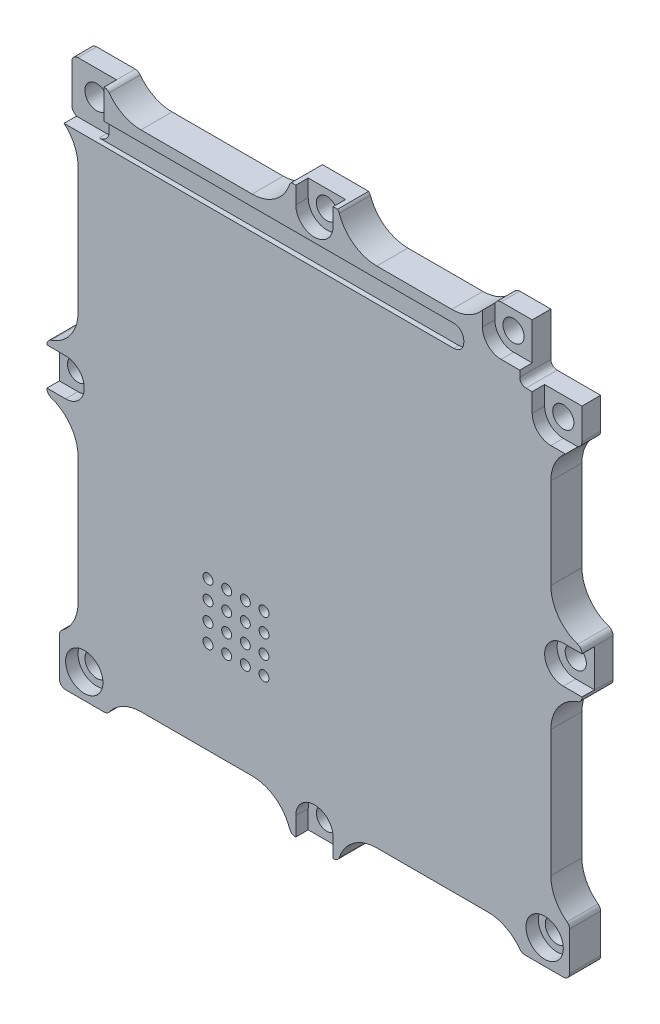
SolidWorks part; units mm, degrees
material "6061-T6 (SS)"
ref_plane "Front Plane" through (0, 0, 0) normal (0, 0, 1) x (1, 0, 0)
ref_plane "Top Plane" through (0, 0, 0) normal (0, 1, 0) x (1, 0, 0)
ref_plane "Right Plane" through (0, 0, 0) normal (1, 0, 0) x (0, 0, -1)
sketch "Sketch1" plane through (0, 0, 0) normal (0, 0, 1) x (1, 0, 0)
  line L0 (43, 3.0525) -> (43, -3.0525)
  line L1 (-40, 43.5) -> (-9.9117, 43.5) construction
  line L2 (-41, 42.5) -> (-41, 9.9642) construction
  line L3 (-40, -43.5) -> (-9.9117, -43.5) construction
  line L4 (41, 35.5) -> (41, 10.6494) construction
  line L5 (-43, -3.0525) -> (-43, 3.0525)
  line L6 (3.0525, -45.5) -> (-3.0525, -45.5)
  line L7 (3.0525, 45.5) -> (-3.0525, 45.5)
  line L8 (41, -24.3564) -> (41, -42.5) construction
  line L9 (10.0167, -43.5) -> (40, -43.5) construction
  line L10 (-41, -9.9642) -> (-41, -42.5) construction
  line L11 (10.0167, 43.5) -> (33, 43.5) construction
  line L12 (38, 24.5755) -> (38, 10.0167)
  line L14 (41, 35.5) -> (41, 30.5)
  line L15 (22.0755, 40.5) -> (10.0167, 40.5)
  line L17 (33, 43.5) -> (28, 43.5)
  line L18 (38, -10.0167) -> (38, -30.3815)
  line L20 (41, -42.5) -> (41, -36.3061)
  line L21 (-10.0167, 40.5) -> (-27.8815, 40.5)
  line L22 (-40, 43.5) -> (-33.8061, 43.5)
  line L23 (-41, 42.5) -> (-41, 36.3061)
  line L24 (-38, 30.3815) -> (-38, 10.0167)
  line L25 (-38, -10.0167) -> (-38, -30.3815)
  line L26 (-41, -42.5) -> (-41, -36.3061)
  line L27 (-40, -43.5) -> (-33.8061, -43.5)
  line L28 (-10.0167, -40.5) -> (-27.8815, -40.5)
  line L29 (27.8815, -40.5) -> (10.0167, -40.5)
  line L30 (40, -43.5) -> (33.8061, -43.5)
  line L31 (33, 43.5) -> (33, 36.5)
  line L32 (41, 35.5) -> (34, 35.5)
  arc A0 (-41, -42.5) -> (-40, -43.5) centre (-40, -42.5) ccw
  arc A1 (40, -43.5) -> (41, -42.5) centre (40, -42.5) ccw
  arc A3 (-40, 43.5) -> (-41, 42.5) centre (-40, 42.5) ccw
  circle A12 centre (40, 0) radius 1.7
  circle A13 centre (0, 42.5) radius 1.7
  circle A14 centre (-40, 0) radius 1.7
  circle A15 centre (0, -42.5) radius 1.7
  arc A24 (4, 44.8197) -> (3.0525, 45.5) centre (3.0525, 44.5) ccw
  arc A25 (-3.0525, 45.5) -> (-4, 44.8197) centre (-3.0525, 44.5) ccw
  arc A26 (43, -3.0525) -> (42.3197, -4) centre (42, -3.0525) cw
  arc A27 (43, 3.0525) -> (42.3197, 4) centre (42, 3.0525) ccw
  arc A28 (4, -44.8197) -> (3.0525, -45.5) centre (3.0525, -44.5) cw
  arc A29 (-3.0525, -45.5) -> (-4, -44.8197) centre (-3.0525, -44.5) cw
  arc A30 (-43, -3.0525) -> (-42.3197, -4) centre (-42, -3.0525) ccw
  arc A31 (-42.3197, 4) -> (-43, 3.0525) centre (-42, 3.0525) ccw
  arc A32 (41, 30.5) -> (40.5918, 29.6939) centre (40, 30.5) cw
  arc A33 (40.5918, 29.6939) -> (38, 24.5755) centre (44.35, 24.5755) ccw
  arc A34 (42.3197, 4) -> (38, 10.0167) centre (44.35, 10.0167) cw
  arc A35 (22.0755, 40.5) -> (27.1939, 43.0918) centre (22.0755, 46.85) ccw
  arc A36 (28, 43.5) -> (27.1939, 43.0918) centre (28, 42.5) ccw
  arc A37 (10.0167, 40.5) -> (4, 44.8197) centre (10.0167, 46.85) cw
  arc A38 (42.3197, -4) -> (38, -10.0167) centre (44.35, -10.0167) ccw
  arc A39 (38, -30.3815) -> (40.5918, -35.5) centre (44.35, -30.3815) ccw
  arc A40 (41, -36.3061) -> (40.5918, -35.5) centre (40, -36.3061) ccw
  arc A41 (-10.0167, 40.5) -> (-4, 44.8197) centre (-10.0167, 46.85) ccw
  arc A42 (-33.8061, 43.5) -> (-33, 43.0918) centre (-33.8061, 42.5) cw
  arc A43 (-41, 36.3061) -> (-40.5918, 35.5) centre (-40, 36.3061) ccw
  arc A44 (-27.8815, 40.5) -> (-33, 43.0918) centre (-27.8815, 46.85) cw
  arc A45 (-38, 30.3815) -> (-40.5918, 35.5) centre (-44.35, 30.3815) ccw
  arc A46 (-42.3197, 4) -> (-38, 10.0167) centre (-44.35, 10.0167) ccw
  arc A47 (-42.3197, -4) -> (-38, -10.0167) centre (-44.35, -10.0167) cw
  arc A48 (-41, -36.3061) -> (-40.5918, -35.5) centre (-40, -36.3061) cw
  arc A49 (-38, -30.3815) -> (-40.5918, -35.5) centre (-44.35, -30.3815) cw
  arc A50 (-33.8061, -43.5) -> (-33, -43.0918) centre (-33.8061, -42.5) ccw
  arc A51 (-27.8815, -40.5) -> (-33, -43.0918) centre (-27.8815, -46.85) ccw
  arc A52 (-4, -44.8197) -> (-10.0167, -40.5) centre (-10.0167, -46.85) ccw
  arc A53 (10.0167, -40.5) -> (4, -44.8197) centre (10.0167, -46.85) ccw
  arc A54 (33.8061, -43.5) -> (33, -43.0918) centre (33.8061, -42.5) cw
  arc A55 (27.8815, -40.5) -> (33, -43.0918) centre (27.8815, -46.85) cw
  arc A56 (33, 36.5) -> (34, 35.5) centre (34, 36.5) ccw
  circle A57 centre (30, 40.5) radius 1.7
  circle A58 centre (38, 32.5) radius 1.7
  point P9 (-41, -43.5)
  point P14 (41, 43.5)
  point P17 (-41, 43.5)
  point P26 (43, 0)
  point P27 (-43, 0)
  point P28 (0, -45.5)
  point P29 (0, 45.5)
  dimension "D3" = 1
  dimension "D4" = 3
  dimension "D11" = 3
  dimension "D12" = 3.4
  dimension "D19" = 38
  dimension "D20" = 1
  dimension "D23" = 6.35
  dimension "D24" = 1
  dimension "D28" = 6.35
  dimension "D31" = 1
  dimension "D5" = 3
  dimension "D6" = 3
  dimension "D7" = 3
  dimension "D8" = 76
  dimension "D9" = 81
  dimension "D10" = 3
  dimension "D13" = 2
  dimension "D14" = 2
  dimension "D15" = 2
  dimension "D16" = 2
  dimension "D17" = 3
  dimension "D18" = 3
  dimension "D21" = 8
  dimension "D22" = 40.5
  dimension "D25" = 5
  dimension "D26" = 5
  dimension "D27" = 5
  dimension "D29" = 5
  dimension "D30" = 5
  dimension "D32" = 5
  dimension "D33" = 5
  dimension "D34" = 5
  dimension "D35" = 5
  dimension "D36" = 3
  dimension "D37" = 3
  dimension "D38" = 3
  dimension "D39" = 3
extrude "Boss-Extrude1" add sketch "Sketch1" against normal blind 5
sketch "Sketch2" plane through (0, 0, -5) normal (0, 0, -1) x (-1, 0, 0)
  line L0 (-20, 37.5) -> (20, 37.5)
  line L1 (35, 22.5) -> (35, -22.5)
  line L2 (-20, -37.5) -> (20, -37.5)
  line L3 (-35, -22.5) -> (-35, 22.5)
  arc A1 (-20, 37.5) -> (-35, 22.5) centre (-20, 22.5) ccw
  arc A3 (20, 37.5) -> (35, 22.5) centre (20, 22.5) cw
  arc A7 (35, -22.5) -> (20, -37.5) centre (20, -22.5) cw
  arc A9 (-35, -22.5) -> (-20, -37.5) centre (-20, -22.5) ccw
  point P13 (35, 0)
  point P14 (0, 37.5)
  dimension "D1" = 15
  dimension "D2" = 70
  dimension "D3" = 75
extrude "Cut-Extrude1" cut sketch "Sketch2" against normal blind 2 contours L0 A3 L1 A7 L2 A9 L3 A1
sketch "Sketch3" plane through (0, 0, 0) normal (0, 0, 1) x (1, 0, 0)
  line L0 (33.8061, -43.5) -> (40, -43.5) construction
  line L1 (40, 3) -> (43, 3)
  line L2 (40, -3) -> (43, -3)
  line L3 (43, 3) -> (43, -3)
  line L4 (43, -3.0525) -> (43, 3.0525) construction
  line L5 (-40, 3) -> (-43, 3)
  line L6 (-40, -3) -> (-43, -3)
  line L7 (-43, -3) -> (-43, 3)
  line L8 (-43, 3.0525) -> (-43, -3.0525) construction
  line L9 (41, -42.5) -> (41, -36.3061) construction
  line L10 (-40, -43.5) -> (-33.8061, -43.5) construction
  line L11 (-41, -36.3061) -> (-41, -42.5) construction
  line L12 (-41, 42.5) -> (-41, 36.3061) construction
  line L13 (-33.8061, 43.5) -> (-40, 43.5) construction
  line L16 (-3, 42.5) -> (-3, 45.5)
  line L17 (3, 42.5) -> (3, 45.5)
  line L18 (-3, 45.5) -> (3, 45.5)
  line L19 (3.0525, 45.5) -> (-3.0525, 45.5) construction
  line L20 (-3, -42.5) -> (-3, -45.5)
  line L21 (3, -42.5) -> (3, -45.5)
  line L22 (-3, -45.5) -> (3, -45.5)
  line L23 (-3.0525, -45.5) -> (3.0525, -45.5) construction
  line L24 (38, 29.5) -> (40.3411, 29.5)
  line L25 (35, 32.5) -> (35, 35.5)
  line L26 (41, 35.5) -> (34, 35.5) construction
  line L27 (30, 37.5) -> (33, 37.5)
  line L28 (33, 36.5) -> (33, 43.5) construction
  line L29 (27, 40.5) -> (27, 42.8411)
  line L30 (41, 30.5) -> (41, 35.5) construction
  line L31 (33, 43.5) -> (28, 43.5) construction
  line L32 (41, 35.5) -> (35, 35.5)
  line L33 (41, 30.5) -> (41, 35.5)
  line L34 (33, 37.5) -> (33, 43.5)
  line L35 (33, 43.5) -> (28, 43.5)
  arc A0 (-40, -3) -> (-40, 3) centre (-40, 0) ccw
  arc A1 (-3, 42.5) -> (3, 42.5) centre (0, 42.5) ccw
  arc A2 (40, 3) -> (40, -3) centre (40, 0) ccw
  arc A3 (3, -42.5) -> (-3, -42.5) centre (0, -42.5) ccw
  circle A5 centre (-37, 39.5) radius 3
  circle A6 centre (-37, -39.5) radius 3
  circle A7 centre (37, -39.5) radius 3
  arc A8 (27, 40.5) -> (30, 37.5) centre (30, 40.5) ccw
  arc A9 (35, 32.5) -> (38, 29.5) centre (38, 32.5) ccw
  circle A10 centre (30, 40.5) radius 1.7 construction
  circle A11 centre (38, 32.5) radius 1.7 construction
  arc A16 (40.5918, 29.6939) -> (38, 24.5755) centre (44.35, 24.5755) ccw construction
  arc A17 (22.0755, 40.5) -> (27.1939, 43.0918) centre (22.0755, 46.85) ccw construction
  arc A18 (40.5918, 29.6939) -> (41, 30.5) centre (40, 30.5) ccw construction
  arc A19 (28, 43.5) -> (27.1939, 43.0918) centre (28, 42.5) ccw construction
  arc A20 (40.5918, 29.6939) -> (41, 30.5) centre (40, 30.5) ccw
  arc A21 (40.5918, 29.6939) -> (40.3411, 29.5) centre (44.35, 24.5755) ccw
  arc A22 (28, 43.5) -> (27.1939, 43.0918) centre (28, 42.5) ccw
  arc A23 (27, 42.8411) -> (27.1939, 43.0918) centre (22.0755, 46.85) ccw
  dimension "D1" = 6
  dimension "D2" = 4
  dimension "D3" = 4
  dimension "D6" = 4
  dimension "D7" = 4
  dimension "D8" = 4
  dimension "D9" = 4
extrude "Cut-Extrude2" cut sketch "Sketch3" against normal blind 2
sketch "Sketch4" plane through (0, 0, -2) normal (0, 0, 1) x (1, 0, 0)
  circle A0 centre (-37, 39.5) radius 1.9
  circle A2 centre (37, -39.5) radius 1.9
  circle A3 centre (-37, -39.5) radius 1.9
  circle A4 centre (-37, 39.5) radius 3 construction
  circle A6 centre (-37, -39.5) radius 3 construction
  circle A7 centre (37, -39.5) radius 3 construction
  dimension "D1" = 3.8
extrude "Cut-Extrude3" cut sketch "Sketch4" against normal up to surface (3 mm away) up to face at (0, 0, -5)
sketch "Sketch5" plane through (0, 0, 0) normal (0, 0, 1) x (1, 0, 0)
  line L0 (-17.109, -19.609) -> (-34, -19.609) construction
  line L1 (-17.109, -19.609) -> (-14.109, -19.609) construction
  line L2 (20, -37.5) -> (-20, -37.5) construction
  line L3 (-35, 22.5) -> (-35, -22.5) construction
  line L4 (-17.109, -19.609) -> (-17.109, -22.609) construction
  line L5 (-17.109, -19.609) -> (-17.109, -16.609) construction
  circle A0 centre (-17.109, -19.609) radius 16.891 construction
  circle A2 centre (-17.109, -19.609) radius 0.8
  circle A3 centre (-14.109, -19.609) radius 0.8
  circle A4 centre (-11.109, -19.609) radius 0.8
  circle A5 centre (-8.109, -19.609) radius 0.8
  circle A6 centre (-17.109, -22.609) radius 0.8
  circle A7 centre (-14.109, -22.609) radius 0.8
  circle A8 centre (-11.109, -22.609) radius 0.8
  circle A9 centre (-8.109, -22.609) radius 0.8
  circle A10 centre (-17.109, -25.609) radius 0.8
  circle A11 centre (-14.109, -25.609) radius 0.8
  circle A12 centre (-11.109, -25.609) radius 0.8
  circle A13 centre (-8.109, -25.609) radius 0.8
  circle A14 centre (-17.109, -16.609) radius 0.8
  circle A15 centre (-14.109, -16.609) radius 0.8
  circle A16 centre (-11.109, -16.609) radius 0.8
  circle A17 centre (-8.109, -16.609) radius 0.8
  dimension "D6" = 3
  dimension "D7" = 16.891
  dimension "D9" = 3
  dimension "D2" = 1.6
  dimension "D3" = 4
  dimension "D4" = 3
  dimension "D5" = 3
  dimension "D8" = 2
  dimension "D10" = 17.891
  dimension "D11" = 17.891
extrude "Cut-Extrude4" cut sketch "Sketch5" against normal up to surface (3 mm away) up to face at (0, 0, -3)
sketch "Sketch7" plane through (0, 0, 0) normal (0, 0, 1) x (1, 0, 0)
  line L0 (-10.0167, 40.5) -> (-27.8815, 40.5) construction
  line L1 (22.4125, 38.73) -> (-34.1005, 38.73)
  line L2 (24, 37.1425) -> (24, 36.8175)
  line L3 (22.4125, 35.23) -> (-37, 35.23)
  line L5 (38, 10.0167) -> (38, 24.5755) construction
  line L6 (-37, 36.5) -> (-37, 35.23)
  circle A2 centre (-37, 39.5) radius 3 construction
  arc A3 (-37, 36.5) -> (-34.1005, 38.73) centre (-37, 39.5) ccw
  arc A4 (22.4125, 38.73) -> (24, 37.1425) centre (22.4125, 37.1425) cw
  arc A5 (24, 36.8175) -> (22.4125, 35.23) centre (22.4125, 36.8175) cw
  dimension "D4" = 1.5875
  dimension "D1" = 3.5
  dimension "D2" = 1.77
  dimension "D3" = 14
extrude "Cut-Extrude8" cut sketch "Sketch7" against normal blind 0.8 contours L3 L6 A3 L1 A4 L2 A5
fillet "Fillet1" radius 1.5875 1 edges at (-37, 35.23, -0.4)
sketch "Sketch8" plane through (0, 0, 0) normal (0, 0, 1) x (1, 0, 0)
  line L0 (-33.8061, 43.5) -> (-33.8061, 35.23)
  line L1 (22.4125, 35.23) -> (-35.4446, 35.23) construction
  line L2 (-33.8061, 35.23) -> (-41, 35.23)
  line L3 (-41, 35.23) -> (-41, 43.5)
  line L4 (-41, 43.5) -> (-33.8061, 43.5)
  line L5 (-33.8061, 43.5) -> (-40, 43.5) construction
  line L6 (-41, 42.5) -> (-41, 36.3061) construction
extrude "Cut-Extrude9" cut sketch "Sketch8" against normal up to surface (2 mm away) up to face at (-35.1, 39.5, -2)
fillet "Fillet2" radius 1.5875 1 edges at (-33.8061, 35.23, -1.4)
sketch "Sketch9" plane through (0, 0, 0) normal (1, 0, 0) x (0, 0, -1)
  line L0 (5, 40.5) -> (5, 44.8197) construction
  line L1 (5, 45.5) -> (0, 45.5)
  line L2 (5, 45.5) -> (5, 45.25)
  line L3 (5, 45.25) -> (0, 45.25)
  line L4 (0, 45.5) -> (0, 45.25)
  line L5 (0, 43.0918) -> (0, 40.5) construction
  line L6 (5, 45.5) -> (0, 45.5) construction
  line L8 (5, 44.2) -> (5, 40.8) construction
  point P12 (5, 42.5)
  dimension "D1" = 2.75
extrude "Cut-Extrude11" cut sketch "Sketch9" against normal mid plane 10
